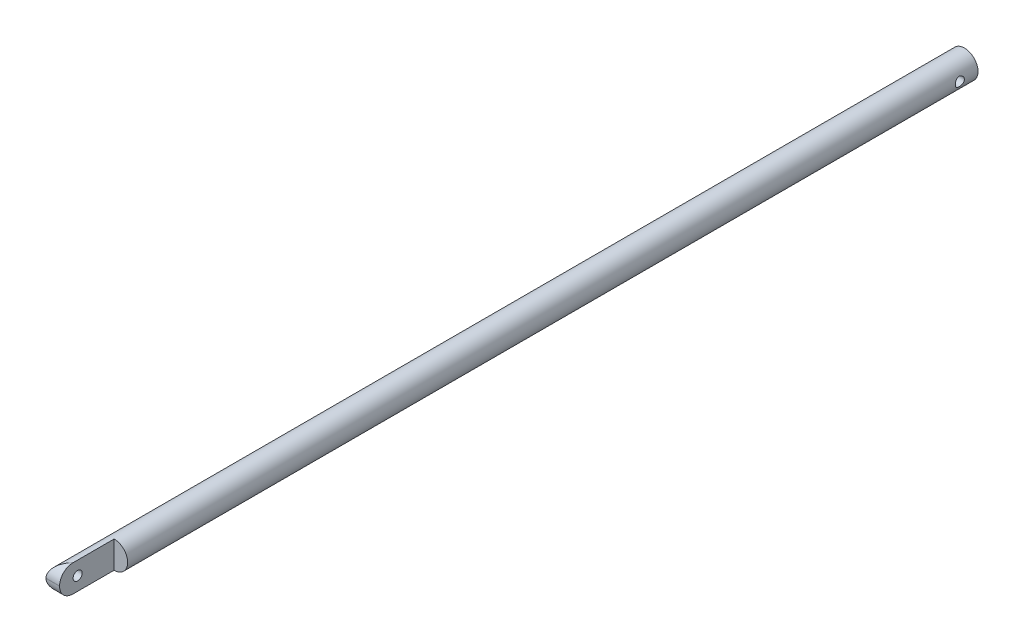
SolidWorks part; units mm, degrees
ref_plane "前视基准面" through (0, 0, 0) normal (0, 0, 1) x (1, 0, 0)
ref_plane "上视基准面" through (0, 0, 0) normal (0, 1, 0) x (1, 0, 0)
ref_plane "右视基准面" through (0, 0, 0) normal (1, 0, 0) x (0, 0, -1)
sketch "草图1" plane through (0, 0, 0) normal (0, 0, 1) x (1, 0, 0)
  circle A0 centre (0, 0) radius 1.49
  dimension "D1" = 2.98
extrude "凸台-拉伸1" add sketch "草图1" along normal blind 100
sketch "草图2" plane through (0, 0, 0) normal (0, 1, 0) x (1, 0, 0)
  line L0 (0, -100) -> (0, 2.1743) construction
  line L1 (-1.49, -100) -> (3.1896, -100) construction
  line L2 (1.49, -100) -> (1.49, 0) construction
  line L3 (0, -100) -> (1.49, -100)
  line L4 (0, -100) -> (0, -94)
  line L5 (0, -94) -> (1.49, -94)
  line L6 (1.49, -100) -> (1.49, -94)
  dimension "D1" = 6
sketch "草图4" plane through (0, 0, 0) normal (1, 0, 0) x (0, 0, -1)
  line L0 (3.5736, 0) -> (-21.075, 0) construction
  circle A0 centre (-2.5, 0) radius 0.5
  dimension "D1" = 1
  dimension "D2" = 2.5
extrude "切除-拉伸3" cut sketch "草图4" against normal through all both and the other way through all contours A0 region at (0, 0, 2.5)
extrude "切除-拉伸7" cut sketch "草图2" against normal through all both and the other way through all
sketch "草图6" plane through (0, 0, 0) normal (1, 0, 0) x (0, 0, -1)
  line L0 (-100, 0) -> (-65.2989, 0) construction
  line L1 (-100, -1.49) -> (-100, 1.49) construction
  line L2 (-94, -1.49) -> (-100, -1.49) construction
  line L3 (-94, 1.49) -> (-100, 1.49) construction
  line L4 (-75.01, 1.49) -> (-98.52, 1.49)
  line L5 (-100, 0.01) -> (-100, -0.01)
  line L6 (-98.52, -1.49) -> (-75.01, -1.49)
  line L7 (-100, 3.7724) -> (-100, -4.7722) construction
  line L8 (-100, -1.49) -> (-100, 1.49) construction
  circle A0 centre (-98.01, 0) radius 0.5
  arc A2 (-100, 0.01) -> (-98.52, 1.49) centre (-98.52, 0.01) cw
  arc A3 (-98.52, -1.49) -> (-100, -0.01) centre (-98.52, -0.01) cw
  point P22 (-100, 1.49)
  point P25 (-100, -1.49)
  line M1 (-100, 1.49) -> (-100, -1.49)
  line M2 (-100, -1.49) -> (-94, -1.49)
  line M4 (-94, 1.49) -> (-100, 1.49)
  dimension "D1" = 1
  dimension "D3" = 1.48
  dimension "D4" = 1.48
  dimension "D2" = 1.99
extrude "切除-拉伸8" cut sketch "草图6" against normal blind 10 contours A2 M1 M4 | A3 M2 M1 | A0 region at (0, -1.1594, 99.6694) region at (0, 1.1594, 99.6694) region at (0, 0, 98.01)
sketch "草图7" plane through (0, 0, 0) normal (0, 0, -1) x (-1, 0, 0)
  circle A0 centre (0, 0) radius 1.49
extrude "切除-拉伸9" cut sketch "草图7" against normal blind 0.5
